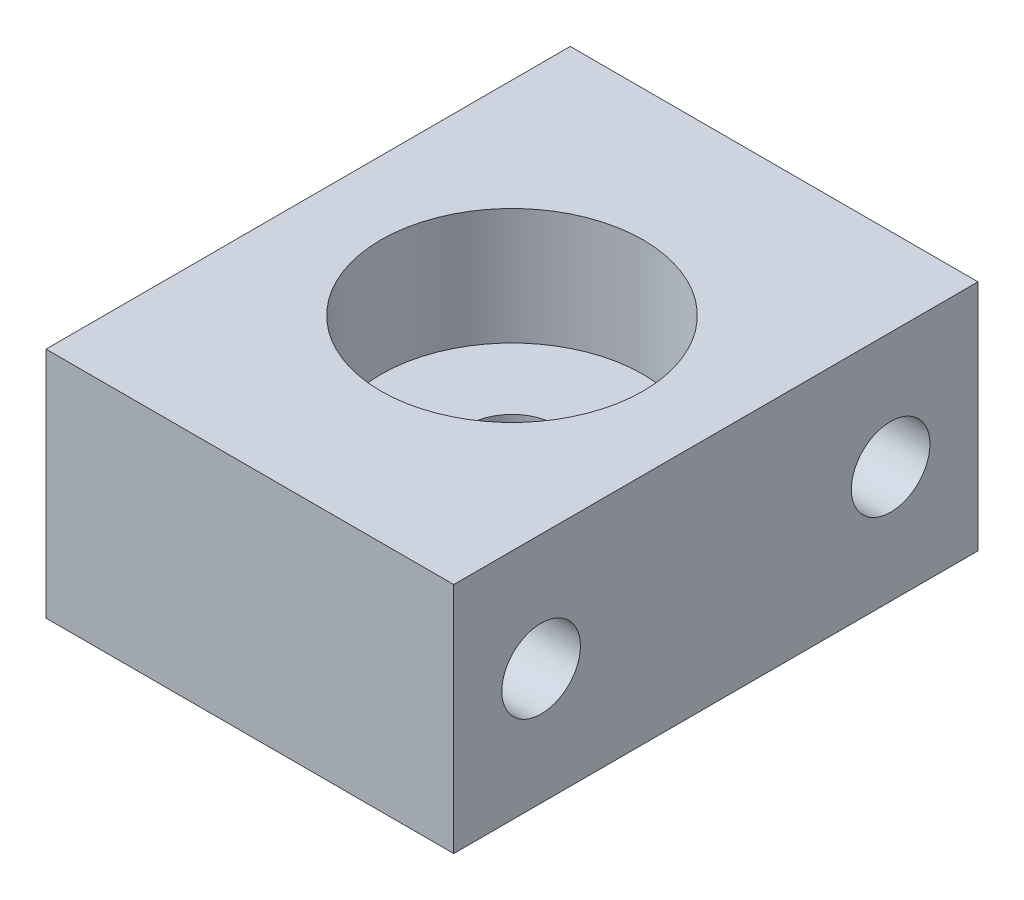
SolidWorks part; units mm, degrees
ref_plane "前视基准面" through (0, 0, 0) normal (0, 0, 1) x (1, 0, 0)
ref_plane "上视基准面" through (0, 0, 0) normal (0, 1, 0) x (1, 0, 0)
ref_plane "右视基准面" through (0, 0, 0) normal (1, 0, 0) x (0, 0, -1)
sketch "草图2" plane through (0, 0, 0) normal (0, 0, 1) x (1, 0, 0)
  line L0 (-50, -999.1095) -> (-50, 49000.8905) construction
  line L1 (-7, -4) -> (7, -4)
  line L2 (-7, -4) -> (-7, 4)
  line L3 (-7, 4) -> (7, 4)
  line L4 (7, -4) -> (7, 4)
  line L5 (-7, -4) -> (7, 4) construction
  line L6 (-7, 4) -> (7, -4) construction
  point P0 (0, 0)
  dimension "D1" = 14
  dimension "D2" = 8
  dimension "D3" = 50
extrude "凸台-拉伸2" add sketch "草图2" along normal mid plane 18
sketch "草图3" plane through (0, 0, 0) normal (1, 0, 0) x (0, 0, -1)
  line L0 (0, -1000) -> (0, 1000) construction
  circle A0 centre (6, 0) radius 1.35
  circle A1 centre (-6, 0) radius 1.35
  point P8 (0, 0)
  point P10 (0, 0)
  point P11 (0, 0)
  dimension "D1" = 2.7
  dimension "D2" = 6
extrude "切除-拉伸1" cut sketch "草图3" against normal through all both and the other way through all
extrude "凸台-拉伸3" add sketch "草图3<2>" along normal mid plane 6
sketch "草图3<2>" plane through (0, 0, 0) normal (1, 0, 0) x (0, 0, -1) same geometry as "草图3"
sketch "草图4" plane through (0, -4, 0) normal (0, -1, 0) x (1, 0, 0)
  line L1 (0, -5) -> (0, 5) construction
  circle A1 centre (0, -5) radius 1.5
  circle A2 centre (0, 5) radius 1.5
  dimension "D1" = 3
  dimension "D2" = 10
extrude "切除-拉伸2" [suppressed] cut sketch "草图4" against normal blind 10
sketch "草图5" [suppressed] plane through (0, 4, 0) normal (0, 1, 0) x (1, 0, 0)
  line L0 (-49.7494, 0) -> (0.2506, 0) construction
  circle A0 centre (-49.7494, 0) radius 50 construction
  dimension "D1" = 100
sketch "草图6" plane through (0, -4, 0) normal (0, -1, 0) x (1, 0, 0)
  circle A0 centre (0, 0) radius 1.5
  dimension "D1" = 3
extrude "切除-拉伸3" cut sketch "草图6" against normal blind 10
sketch "草图7" plane through (0, 4, 0) normal (0, -1, 0) x (1, 0, 0)
  circle A0 centre (0, 0) radius 4.5
  dimension "D1" = 9
extrude "切除-拉伸4" cut sketch "草图7" along normal blind 4
